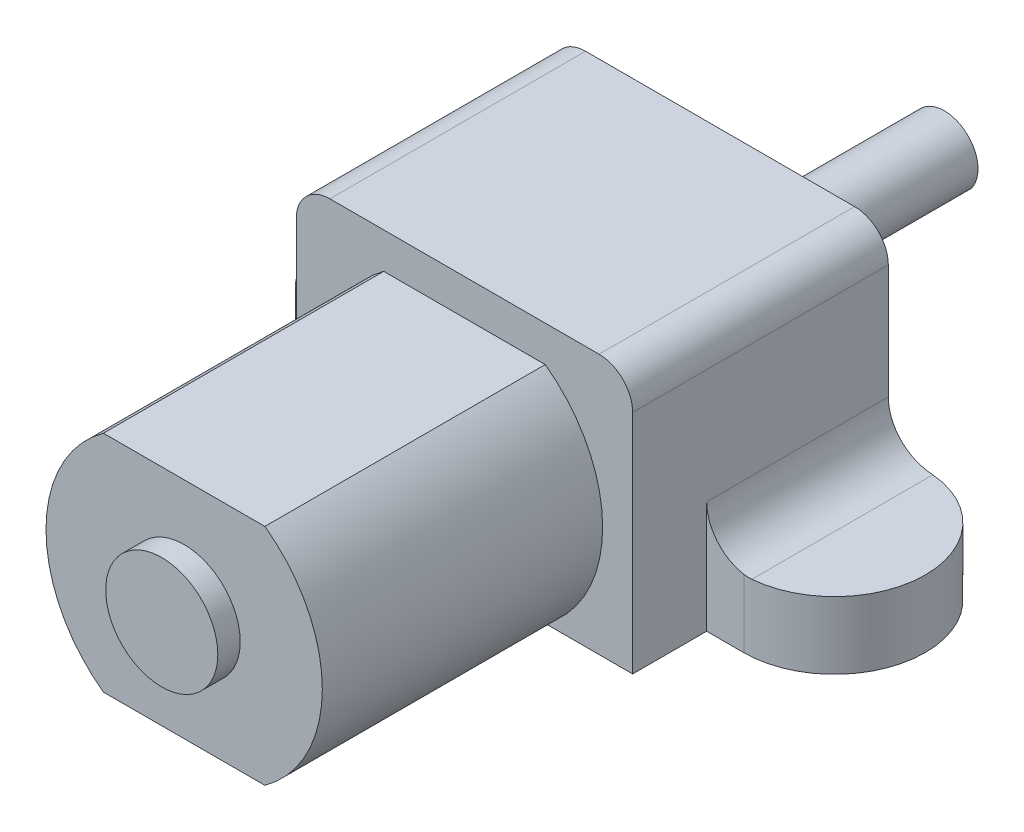
SolidWorks part; units mm, degrees
ref_plane "Přední rovina" through (0, 0, 0) normal (0, 0, 1) x (1, 0, 0)
ref_plane "Horní rovina" through (0, 0, 0) normal (0, 1, 0) x (1, 0, 0)
ref_plane "Pravá rovina" through (0, 0, 0) normal (1, 0, 0) x (0, 0, -1)
sketch "Skica1" plane through (0, 0, 0) normal (0, 0, 1) x (1, 0, 0)
  line L1 (-7.5, -5.8) -> (7.5, -5.8)
  line L2 (-7.5, -5.8) -> (-7.5, 5.8)
  line L3 (-7.5, 5.8) -> (7.5, 5.8)
  line L4 (7.5, -5.8) -> (7.5, 5.8)
  line L5 (-7.5, -5.8) -> (7.5, 5.8) construction
  line L6 (-7.5, 5.8) -> (7.5, -5.8) construction
  point P0 (0, 0)
  dimension "D1" = 15
  dimension "D2" = 11.6
extrude "Přidat vysunutím1" add sketch "Skica1" along normal blind 11.4
sketch "Skica2" plane through (0, 0, 11.4) normal (0, 0, 1) x (1, 0, 0)
  line L0 (0, 5.1795) -> (0, -6.7804) construction
  line L1 (-7.5, -5.8) -> (7.5, -5.8) construction
  line L2 (-3.6, -5.8) -> (3.6, -5.8)
  line L4 (-3.6, 4.1991) -> (3.6, 4.1991)
  line L13 (7.5, 5.8) -> (-7.5, 5.8) construction
  arc A0 (-3.6, 4.1991) -> (-3.6, -5.8) centre (0, -0.8005) ccw
  arc A1 (3.6, -5.8) -> (3.6, 4.1991) centre (0, -0.8005) ccw
  point P0 (0, 0)
  dimension "D1" = 7.2
  dimension "D2" = 1.6009
  dimension "D3" = 7.2
extrude "Přidat vysunutím3" add sketch "Skica2" along normal blind 12.5
fillet "Zaoblit1" radius 1.5 1 edges at (7.5, 5.8, 5.7)
fillet "Zaoblit2" radius 1.5 1 edges at (-7.5, 5.8, 5.7)
sketch "Skica3" plane through (0, 0, 0) normal (0, 0, -1) x (-1, 0, 0)
  line L0 (-1.2, -0.9) -> (1.2, -0.9)
  arc A0 (1.2, -0.9) -> (-1.2, -0.9) centre (0, 0) ccw
  dimension "D2" = 2.4
  dimension "D1" = 3
extrude "Přidat vysunutím4" add sketch "Skica3" along normal blind 10
sketch "Skica4" plane through (-7.5, 0, 0) normal (-1, 0, 0) x (0, 0, 1)
  line L0 (0, -5.8) -> (0, -2.8)
  line L1 (0, 4.3) -> (0, -5.8) construction
  line L2 (0, -2.8) -> (8.1, -2.8)
  line L3 (8.1, -2.8) -> (8.1, -5.8)
  line L4 (11.4, -5.8) -> (0, -5.8) construction
  line L5 (8.1, -5.8) -> (0, -5.8)
  dimension "D1" = 8.1
  dimension "D2" = 3
extrude "Přidat vysunutím5" add sketch "Skica4" along normal blind 5.7
sketch "Skica7" plane through (0, -2.8, 0) normal (0, 1, 0) x (1, 0, 0)
  line L0 (-13.2, -8.1) -> (-13.2, 0) construction
  line L1 (-13.2, 0) -> (-7.5, 0) construction
  line L2 (-9.1436, 0) -> (-13.2, 0)
  line L3 (-13.2, 0) -> (-13.2, -8.1)
  line L4 (-13.2, -8.1) -> (-9.4667, -8.1)
  line L5 (-13.2, -8.1) -> (-7.5, -8.1) construction
  arc A0 (-13.2, -4.05) -> (-9.4667, -8.1) centre (-9.1436, -4.0564) ccw
  arc A1 (-9.1436, 0) -> (-13.2, -4.05) centre (-9.1436, -4.0564) ccw
  line M2 (-7.5, 0) -> (-13.2, 0)
  line M3 (-13.2, 0) -> (-13.2, -8.1)
  line M4 (-13.2, -8.1) -> (-7.5, -8.1)
extrude "Odebrat vysunutím3" cut sketch "Skica7" against normal blind 10 contours A0 M3 M4 | A1 M2 M3
fillet "Zaoblit3" radius 2 3 edges at (-7.5, -2.8, 4.05) (-8.4833, -2.8, 8.1) (-8.3218, -2.8, 0)
sketch "Skica10" plane through (7.5, 0, 0) normal (1, 0, 0) x (0, 0, -1)
  line L0 (-8.1, -5.8) -> (-8.1, -2.8)
  line L1 (-8.1, -2.8) -> (0, -2.8)
  line L2 (0, -2.8) -> (0, -5.8)
  line L3 (0, -5.8) -> (-8.1, -5.8)
  line L4 (0, -5.8) -> (0, 4.3) construction
  line L5 (-11.4, -5.8) -> (0, -5.8) construction
  dimension "D1" = 8.1
  dimension "D2" = 3
extrude "Přidat vysunutím6" add sketch "Skica10" along normal blind 5.7
sketch "Skica11" plane through (0, -2.8, 0) normal (0, 1, 0) x (1, 0, 0)
  line L0 (13.2, 0) -> (13.2, -8.1) construction
  line L1 (9.1718, -8.1) -> (13.2, -8.1)
  line L2 (13.2, -8.1) -> (13.2, 0)
  line L3 (13.2, 0) -> (9.128, 0)
  line L4 (13.2, -8.1) -> (7.5, -8.1) construction
  line L5 (13.2, 0) -> (7.5, 0) construction
  arc A0 (13.2, -4.05) -> (9.1718, -8.1) centre (9.1499, -4.05) cw
  arc A1 (13.2, -4.05) -> (9.128, 0) centre (9.1499, -4.05) ccw
  line M2 (7.5, -8.1) -> (13.2, -8.1)
  line M3 (13.2, -8.1) -> (13.2, 0)
  line M4 (13.2, 0) -> (7.5, 0)
extrude "Odebrat vysunutím5" cut sketch "Skica11" against normal blind 5.7 contours A0 M3 M2 | A1 L2 M4
fillet "Zaoblit4" radius 2 3 edges at (7.5, -2.8, 4.05) (8.3359, -2.8, 8.1) (8.3359, -2.8, 0)
sketch "Skica12" plane through (0, 0, 23.9) normal (0, 0, 1) x (1, 0, 0)
  line L0 (0, 4.1991) -> (0, -5.8) construction
  line L1 (3.6, 4.1991) -> (-3.6, 4.1991) construction
  line L2 (-3.6, -5.8) -> (3.6, -5.8) construction
  line L3 (0, -0.8005) -> (6.1608, -0.8005) construction
  line L4 (0, -0.8005) -> (-6.1608, -0.8005) construction
  arc A0 (3.6, -5.8) -> (3.6, 4.1991) centre (0, -0.8005) ccw construction
  arc A1 (-3.6, 4.1991) -> (-3.6, -5.8) centre (0, -0.8005) ccw construction
  circle A2 centre (0, -0.8005) radius 2.5
  dimension "D1" = 5
extrude "Přidat vysunutím7" add sketch "Skica12" along normal blind 1
